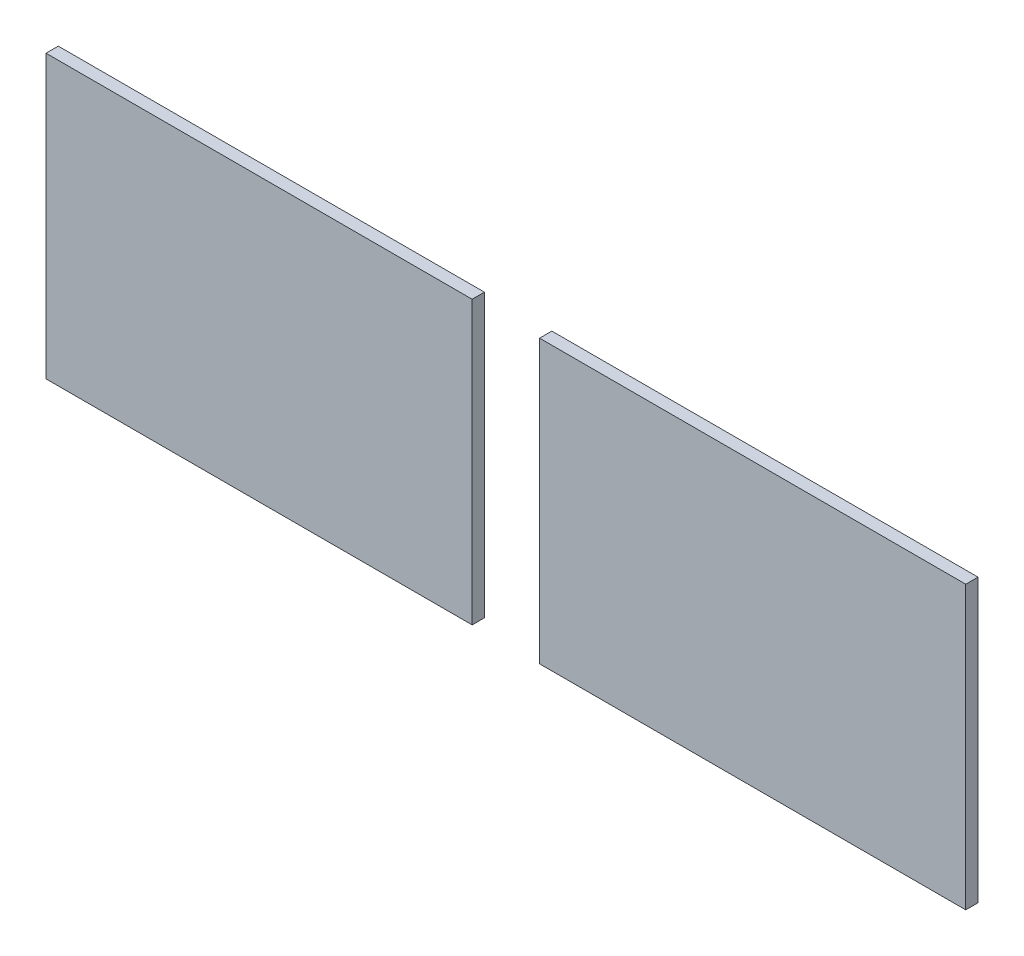
SolidWorks part; units mm, degrees
material "Pine"
ref_plane "Front Plane" through (0, 0, 0) normal (0, 0, 1) x (1, 0, 0)
ref_plane "Top Plane" through (0, 0, 0) normal (0, 1, 0) x (1, 0, 0)
ref_plane "Right Plane" through (0, 0, 0) normal (1, 0, 0) x (0, 0, -1)
sketch "Sketch1" plane through (0, 0, 0) normal (0, 0, 1) x (1, 0, 0)
  line L6 (0, 0) -> (900, 0)
  line L10 (0, 0) -> (0, 276)
  line L11 (0, 276) -> (900, 276)
  line L12 (900, 0) -> (900, 276)
  dimension "D3" = 276
  dimension "D1" = 900
extrude "Boss-Extrude1" add sketch "Sketch1" along normal blind 12 contours L10 L11 L12 L6
sketch "Sketch2" plane through (0, 0, 12) normal (0, 0, 1) x (1, 0, 0)
  line L0 (450, 276) -> (450, 0) construction
  line L1 (0, 276) -> (900, 276) construction
  line L2 (0, 0) -> (900, 0) construction
  line L4 (417, 276) -> (483, 276)
  line L5 (417, 276) -> (417, 0)
  line L6 (417, 0) -> (483, 0)
  line L7 (483, 276) -> (483, 0)
  line L8 (417, 276) -> (483, 0) construction
  line L9 (417, 0) -> (483, 276) construction
  point P6 (450, 138)
  dimension "D1" = 66
extrude "Cut-Extrude1" cut sketch "Sketch2" against normal up to surface (12 mm away) up to face at (450, 138, 0)
equation "\"LENGTH\" = 900mm"
equation "\"D1@Sketch1\"=\"LENGTH\""
equation "\"PLY\"= 12mm"
equation "\"D1@Boss-Extrude1\"=\"PLY\""
equation "\"CENTER_BRACE_LENGTH\" = 393mm"
equation "\"D1@Sketch2\"=\"LENGTH\" - \"CENTER_BRACE_LENGTH\" * 2 - \"PLY\" * 4"
equation "\"PANEL_WIDTH\"= \"LENGTH\" - \"CENTER_BRACE_LENGTH\" * 2 - \"PLY\" * 4"
